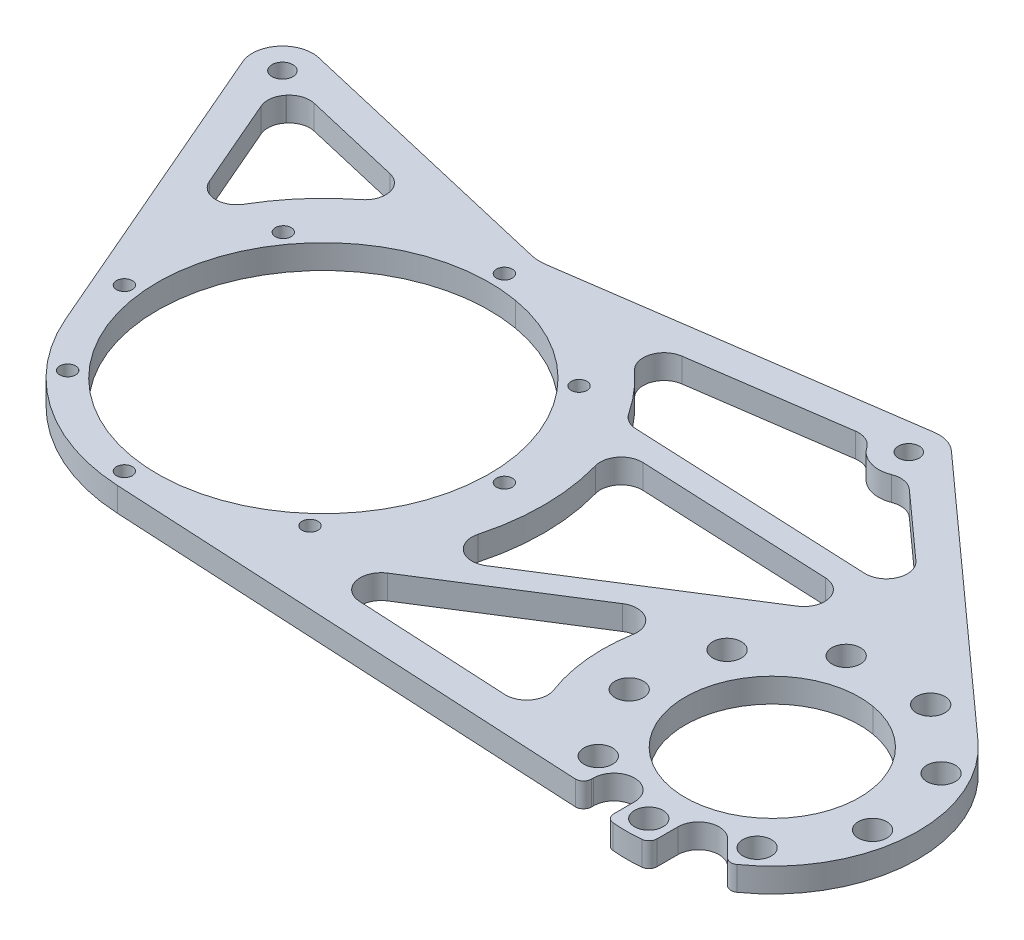
SolidWorks part; units mm, degrees
material "6061-T6 (SS)"
ref_plane "X-Y Datum" through (0, 0, 0) normal (0, 0, 1) x (1, 0, 0)
ref_plane "X-Z Datum" through (0, 0, 0) normal (0, 1, 0) x (1, 0, 0)
ref_plane "Y-Z Datum" through (0, 0, 0) normal (1, 0, 0) x (0, 0, -1)
sketch "Sketch2" plane through (0, 31.3819, 0) normal (0, 1, 0) x (1, 0, 0)
  line L0 (-693.7583, -176.702) -> (-693.7583, -183.2747) construction
  line L1 (-680.0808, -183.2747) -> (-680.0808, -176.702) construction
  line L2 (-668.9846, -172.1058) -> (-663.7197, -177.3707) construction
  line L3 (-693.7583, -176.702) -> (-693.7583, -183.2747)
  line L4 (-680.0808, -183.2747) -> (-680.0808, -176.702)
  line L5 (-668.9846, -172.1058) -> (-663.7197, -177.3707)
  line L6 (-966.641, -0.354) -> (-738.041, -0.354)
  line L7 (-727.7656, -5.5904) -> (-649.7224, -113.0358)
  line L9 (-977.8288, -19.0644) -> (-913.2312, -139.3061)
  line L10 (-706.7583, -177.279) -> (-706.7583, -176.702) construction
  line L11 (-706.7583, -177.279) -> (-706.7583, -176.702)
  line L12 (-861.9259, -171.8334) -> (-709.2983, -179.819)
  line L13 (-858.691, -110.0055) -> (-686.9195, -140.054) construction
  line L14 (-972.26, -24.9963) -> (-955.4664, -39.59) construction
  line L15 (-941.4162, -26.937) -> (-954.1775, -8.712) construction
  line L16 (-751.1929, -14.159) -> (-755.4346, -35.9995) construction
  line L17 (-737.4517, -41.8408) -> (-728.049, -21.6768) construction
  line L18 (-972.26, -24.9963) -> (-955.4664, -39.59)
  line L19 (-941.4162, -26.937) -> (-954.1775, -8.712)
  line L20 (-751.1929, -14.159) -> (-755.4346, -35.9995)
  line L21 (-737.4517, -41.8408) -> (-728.049, -21.6768)
  line L22 (-949.2186, -22.8753) -> (-746.0843, -28.2904)
  line L23 (-739.7146, -30.7335) -> (-656.1751, -105.8723)
  line L24 (-957.9647, -36.1729) -> (-915.5404, -134.527)
  arc A0 (-710.607, -179.4559) -> (-706.7583, -177.279) centre (-709.2983, -177.279) ccw construction
  arc A1 (-693.7583, -176.702) -> (-706.7583, -176.702) centre (-700.2583, -176.702) ccw construction
  arc A2 (-693.7583, -183.2747) -> (-691.4697, -185.8023) centre (-691.2183, -183.2747) ccw construction
  arc A3 (-691.4697, -185.8023) -> (-682.3694, -185.8023) centre (-686.9195, -140.054) ccw construction
  arc A4 (-682.3694, -185.8023) -> (-680.0808, -183.2747) centre (-682.6208, -183.2747) ccw construction
  arc A5 (-668.9846, -172.1058) -> (-680.0808, -176.702) centre (-673.5808, -176.702) ccw construction
  arc A6 (-663.7197, -177.3707) -> (-660.4619, -177.6519) centre (-661.9236, -175.5746) ccw construction
  arc A7 (-660.4619, -177.6519) -> (-710.607, -179.4559) centre (-686.9195, -140.054) ccw construction
  circle A8 centre (-858.691, -110.0055) radius 52.3875 construction
  circle A9 centre (-858.691, -110.0055) radius 61.9125 construction
  circle A10 centre (-738.041, -13.054) radius 12.7 construction
  circle A11 centre (-966.641, -13.054) radius 12.7 construction
  arc A12 (-710.607, -179.4559) -> (-706.7583, -177.279) centre (-709.2983, -177.279) ccw
  arc A13 (-693.7583, -176.702) -> (-706.7583, -176.702) centre (-700.2583, -176.702) ccw
  arc A14 (-693.7583, -183.2747) -> (-691.4697, -185.8023) centre (-691.2183, -183.2747) ccw
  arc A15 (-691.4697, -185.8023) -> (-682.3694, -185.8023) centre (-686.9195, -140.054) ccw
  arc A16 (-682.3694, -185.8023) -> (-680.0808, -183.2747) centre (-682.6208, -183.2747) ccw
  arc A17 (-668.9846, -172.1058) -> (-680.0808, -176.702) centre (-673.5808, -176.702) ccw
  arc A18 (-663.7197, -177.3707) -> (-660.4619, -177.6519) centre (-661.9236, -175.5746) ccw
  arc A19 (-660.4619, -177.6519) -> (-710.607, -179.4559) centre (-686.9195, -140.054) ccw
  circle A20 centre (-858.691, -110.0055) radius 52.3875
  circle A21 centre (-858.691, -110.0055) radius 61.9125
  circle A22 centre (-738.041, -13.054) radius 12.7
  circle A23 centre (-966.641, -13.054) radius 12.7
  circle A24 centre (-901.1618, -148.2463) radius 2.5 construction
  circle A25 centre (-915.528, -115.9793) radius 2.5 construction
  circle A26 centre (-904.9264, -76.4135) radius 2.5 construction
  circle A27 centre (-858.691, -52.8555) radius 2.5 construction
  circle A28 centre (-816.2203, -71.7646) radius 2.5 construction
  circle A29 centre (-801.541, -110.0055) radius 2.5 construction
  circle A30 centre (-820.4502, -152.4762) radius 2.5 construction
  circle A31 centre (-864.6648, -166.8424) radius 2.5 construction
  circle A32 centre (-901.1618, -148.2463) radius 2.5
  circle A33 centre (-915.528, -115.9793) radius 2.5
  circle A34 centre (-904.9264, -76.4135) radius 2.5
  circle A35 centre (-858.691, -52.8555) radius 2.5
  circle A36 centre (-816.2203, -71.7646) radius 2.5
  circle A37 centre (-801.541, -110.0055) radius 2.5
  circle A38 centre (-820.4502, -152.4762) radius 2.5
  circle A39 centre (-864.6648, -166.8424) radius 2.5
  circle A40 centre (-686.9195, -140.054) radius 27.4955 construction
  circle A41 centre (-686.9195, -140.054) radius 27.4955
  circle A42 centre (-711.9883, -169.9297) radius 4.5 construction
  circle A43 centre (-725.3271, -146.8263) radius 4.5 construction
  circle A44 centre (-720.6945, -120.554) radius 4.5 construction
  circle A45 centre (-700.2583, -103.406) radius 4.5 construction
  circle A46 centre (-673.5808, -103.406) radius 4.5 construction
  circle A47 centre (-653.1446, -120.554) radius 4.5 construction
  circle A48 centre (-648.512, -146.8263) radius 4.5 construction
  circle A49 centre (-661.8508, -169.9297) radius 4.5 construction
  circle A50 centre (-686.9195, -179.054) radius 4.5 construction
  circle A51 centre (-711.9883, -169.9297) radius 4.5
  circle A52 centre (-725.3271, -146.8263) radius 4.5
  circle A53 centre (-720.6945, -120.554) radius 4.5
  circle A54 centre (-700.2583, -103.406) radius 4.5
  circle A55 centre (-673.5808, -103.406) radius 4.5
  circle A56 centre (-653.1446, -120.554) radius 4.5
  circle A57 centre (-648.512, -146.8263) radius 4.5
  circle A58 centre (-661.8508, -169.9297) radius 4.5
  circle A59 centre (-686.9195, -179.054) radius 4.5
  circle A60 centre (-966.641, -13.054) radius 3.3
  circle A61 centre (-738.041, -13.054) radius 3.3
  arc A62 (-955.4664, -39.59) -> (-941.4162, -26.937) centre (-949.2186, -32.4003) ccw construction
  arc A63 (-749.3237, -37.1863) -> (-742.8448, -38.4445) centre (-746.0843, -37.8154) ccw construction
  arc A64 (-742.8448, -38.4445) -> (-749.3237, -37.1863) centre (-746.0843, -37.8154) ccw construction
  arc A65 (-755.4346, -35.9995) -> (-737.4517, -41.8408) centre (-746.0843, -37.8154) ccw construction
  arc A66 (-955.4664, -39.59) -> (-941.4162, -26.937) centre (-949.2186, -32.4003) ccw
  arc A67 (-749.3237, -37.1863) -> (-742.8448, -38.4445) centre (-746.0843, -37.8154) ccw
  arc A68 (-742.8448, -38.4445) -> (-749.3237, -37.1863) centre (-746.0843, -37.8154) ccw
  arc A69 (-755.4346, -35.9995) -> (-737.4517, -41.8408) centre (-746.0843, -37.8154) ccw
  circle A70 centre (-949.2186, -32.4003) radius 3.3
  circle A71 centre (-949.2186, -32.4003) radius 9.525
  circle A72 centre (-746.0843, -37.8154) radius 9.525
  point P94 (-949.2186, -32.4003)
  dimension "D1" = 6.6
  dimension "D2" = 6.6
  dimension "D3" = 6.6
extrude "Boss-Extrude1" add sketch "Sketch2" along normal blind 7.62 contours A21 A39 A38 A37 A36 A35 A34 A33 A32 A20 | A18 A19 A12 L11 A13 L3 A14 A15 A16 L4 A17 L5 A59 A58 A57 A56 A55 A54 A53 A52 A51 A41 | L13 A21 L12 A12 A19 | A21 L13 A19 L23 L21 A69 L20 L22 L19 A66 L18 L24 | A69 A72 A68 A67 | A72 L22 L20 | A72 L21 L23 | A71 L24 L18 | A71 L19 L22 | A71 A66 L22 A70 region at (-700.2583, 31.3819, 168.9016) region at (-773.051, 31.3819, 154.3682) region at (-890.9045, 31.3819, 160.8157) region at (-806.8861, 31.3819, 67.2042) region at (-956.9478, 31.3819, 38.0512) region at (-736.2382, 31.3819, 35.8095) region at (-956.6903, 31.3819, 37.8629) region at (-748.9437, 31.3819, 46.6182) region at (-752.4763, 31.3819, 29.8585) region at (-944.5842, 31.3819, 23.8004)
sketch "Sketch3" plane through (0, 31.3819, 0) normal (0, -1, 0) x (1, 0, 0)
  line L1 (-949.2186, 22.8753) -> (-746.0843, 28.2904) construction
  line L5 (-861.9259, 171.8334) -> (-709.2983, 179.819) construction
  line L6 (-977.8288, 19.0644) -> (-913.2312, 139.3061) construction
  line L7 (-727.7656, 5.5904) -> (-649.7224, 113.0358) construction
  line L13 (-751.1929, 14.159) -> (-755.4346, 35.9995) construction
  line L16 (-966.641, 0.354) -> (-738.041, 0.354) construction
  line L19 (-663.7197, 177.3707) -> (-668.9846, 172.1058)
  line L20 (-680.0808, 176.702) -> (-680.0808, 183.2747)
  line L21 (-693.7583, 183.2747) -> (-693.7583, 176.702)
  line L22 (-706.7583, 176.702) -> (-706.7583, 177.279)
  line L23 (-663.7197, 177.3707) -> (-668.9846, 172.1058)
  line L24 (-680.0808, 176.702) -> (-680.0808, 183.2747)
  line L25 (-693.7583, 183.2747) -> (-693.7583, 176.702)
  line L26 (-706.7583, 176.702) -> (-706.7583, 177.279)
  line L28 (-861.9259, 171.8334) -> (-709.2983, 179.819)
  line L29 (-977.8288, 19.0644) -> (-913.2312, 139.3061)
  line L30 (-727.7656, 5.5904) -> (-649.7224, 113.0358)
  line L31 (-966.641, 0.354) -> (-738.041, 0.354)
  line L34 (-737.4517, 41.8408) -> (-728.049, 21.6768) construction
  line L35 (-972.26, 24.9963) -> (-955.4664, 39.59) construction
  line L36 (-947.0539, 23.1246) -> (-856.9722, 44.1471)
  line L37 (-856.9722, 44.1471) -> (-747.4408, 28.3875)
  line L44 (-941.4162, 26.937) -> (-954.1775, 8.712) construction
  line L45 (-957.9647, 36.1729) -> (-915.5404, 134.527) construction
  line L46 (-739.7146, 30.7335) -> (-656.1751, 105.8723) construction
  line L47 (-861.9259, 171.8334) -> (-709.2983, 179.819)
  line L48 (-977.8288, 19.0644) -> (-913.2312, 139.3061)
  line L49 (-727.7656, 5.5904) -> (-649.7224, 113.0358)
  line L50 (-966.641, 0.354) -> (-738.041, 0.354)
  line L51 (-949.2186, 22.8753) -> (-746.0843, 28.2904)
  line L52 (-751.1929, 14.159) -> (-755.4346, 35.9995)
  line L53 (-737.4517, 41.8408) -> (-728.049, 21.6768)
  line L54 (-972.26, 24.9963) -> (-955.4664, 39.59)
  line L55 (-941.4162, 26.937) -> (-954.1775, 8.712)
  line L56 (-957.9647, 36.1729) -> (-915.5404, 134.527)
  line L57 (-739.7146, 30.7335) -> (-656.1751, 105.8723)
  arc A1 (-737.4517, 41.8408) -> (-755.4346, 35.9995) centre (-746.0843, 37.8154) ccw construction
  circle A3 centre (-966.641, 13.054) radius 12.7
  circle A5 centre (-966.641, 13.054) radius 12.7
  circle A7 centre (-738.041, 13.054) radius 12.7
  circle A9 centre (-738.041, 13.054) radius 12.7
  circle A11 centre (-858.691, 110.0055) radius 61.9125
  circle A13 centre (-858.691, 110.0055) radius 61.9125
  circle A15 centre (-858.691, 110.0055) radius 52.3875
  circle A17 centre (-858.691, 110.0055) radius 52.3875
  circle A19 centre (-686.9195, 140.054) radius 27.4955
  circle A21 centre (-686.9195, 140.054) radius 27.4955
  circle A23 centre (-864.6648, 166.8424) radius 2.5
  circle A25 centre (-864.6648, 166.8424) radius 2.5
  circle A27 centre (-820.4502, 152.4762) radius 2.5
  circle A29 centre (-820.4502, 152.4762) radius 2.5
  circle A31 centre (-801.541, 110.0055) radius 2.5
  circle A33 centre (-801.541, 110.0055) radius 2.5
  circle A35 centre (-816.2203, 71.7646) radius 2.5
  circle A37 centre (-816.2203, 71.7646) radius 2.5
  circle A39 centre (-858.691, 52.8555) radius 2.5
  circle A41 centre (-858.691, 52.8555) radius 2.5
  circle A43 centre (-904.9264, 76.4135) radius 2.5
  circle A46 centre (-904.9264, 76.4135) radius 2.5
  circle A47 centre (-915.528, 115.9793) radius 2.5
  circle A48 centre (-915.528, 115.9793) radius 2.5
  circle A49 centre (-901.1618, 148.2463) radius 2.5
  circle A50 centre (-901.1618, 148.2463) radius 2.5
  circle A51 centre (-720.6945, 120.554) radius 4.5
  circle A52 centre (-720.6945, 120.554) radius 4.5
  circle A68 centre (-725.3271, 146.8263) radius 4.5
  circle A69 centre (-725.3271, 146.8263) radius 4.5
  circle A70 centre (-711.9883, 169.9297) radius 4.5
  circle A71 centre (-711.9883, 169.9297) radius 4.5
  circle A72 centre (-738.041, 13.054) radius 3.3
  circle A73 centre (-738.041, 13.054) radius 3.3
  circle A74 centre (-966.641, 13.054) radius 3.3
  circle A75 centre (-966.641, 13.054) radius 3.3
  circle A76 centre (-686.9195, 179.054) radius 4.5
  circle A77 centre (-686.9195, 179.054) radius 4.5
  circle A78 centre (-661.8508, 169.9297) radius 4.5
  circle A79 centre (-661.8508, 169.9297) radius 4.5
  circle A80 centre (-648.512, 146.8263) radius 4.5
  circle A81 centre (-648.512, 146.8263) radius 4.5
  circle A82 centre (-653.1446, 120.554) radius 4.5
  circle A83 centre (-653.1446, 120.554) radius 4.5
  circle A84 centre (-673.5808, 103.406) radius 4.5
  circle A85 centre (-673.5808, 103.406) radius 4.5
  circle A86 centre (-700.2583, 103.406) radius 4.5
  circle A87 centre (-700.2583, 103.406) radius 4.5
  arc A95 (-710.607, 179.4559) -> (-660.4619, 177.6519) centre (-686.9195, 140.054) ccw
  arc A96 (-660.4619, 177.6519) -> (-663.7197, 177.3707) centre (-661.9236, 175.5746) ccw
  arc A97 (-680.0808, 176.702) -> (-668.9846, 172.1058) centre (-673.5808, 176.702) ccw
  arc A98 (-680.0808, 183.2747) -> (-682.3694, 185.8023) centre (-682.6208, 183.2747) ccw
  arc A99 (-682.3694, 185.8023) -> (-691.4697, 185.8023) centre (-686.9195, 140.054) ccw
  arc A100 (-691.4697, 185.8023) -> (-693.7583, 183.2747) centre (-691.2183, 183.2747) ccw
  arc A101 (-706.7583, 176.702) -> (-693.7583, 176.702) centre (-700.2583, 176.702) ccw
  arc A102 (-706.7583, 177.279) -> (-710.607, 179.4559) centre (-709.2983, 177.279) ccw
  arc A103 (-710.607, 179.4559) -> (-660.4619, 177.6519) centre (-686.9195, 140.054) ccw
  arc A104 (-660.4619, 177.6519) -> (-663.7197, 177.3707) centre (-661.9236, 175.5746) ccw
  arc A105 (-680.0808, 176.702) -> (-668.9846, 172.1058) centre (-673.5808, 176.702) ccw
  arc A106 (-680.0808, 183.2747) -> (-682.3694, 185.8023) centre (-682.6208, 183.2747) ccw
  arc A107 (-682.3694, 185.8023) -> (-691.4697, 185.8023) centre (-686.9195, 140.054) ccw
  arc A108 (-691.4697, 185.8023) -> (-693.7583, 183.2747) centre (-691.2183, 183.2747) ccw
  arc A109 (-706.7583, 176.702) -> (-693.7583, 176.702) centre (-700.2583, 176.702) ccw
  arc A110 (-706.7583, 177.279) -> (-710.607, 179.4559) centre (-709.2983, 177.279) ccw
  circle A152 centre (-746.0843, 37.8154) radius 9.525
  circle A153 centre (-746.0843, 37.8154) radius 9.525
  circle A154 centre (-949.2186, 32.4003) radius 9.525
  circle A155 centre (-949.2186, 32.4003) radius 9.525
  circle A156 centre (-949.2186, 32.4003) radius 3.3
  circle A157 centre (-949.2186, 32.4003) radius 3.3
  arc A158 (-941.4162, 26.937) -> (-955.4664, 39.59) centre (-949.2186, 32.4003) ccw construction
  arc A159 (-742.8448, 38.4445) -> (-749.3237, 37.1863) centre (-746.0843, 37.8154) ccw
  arc A160 (-749.3237, 37.1863) -> (-742.8448, 38.4445) centre (-746.0843, 37.8154) ccw
  arc A161 (-742.8448, 38.4445) -> (-749.3237, 37.1863) centre (-746.0843, 37.8154) ccw
  arc A162 (-749.3237, 37.1863) -> (-742.8448, 38.4445) centre (-746.0843, 37.8154) ccw
  arc A163 (-737.4517, 41.8408) -> (-755.4346, 35.9995) centre (-746.0843, 37.8154) ccw
  arc A164 (-941.4162, 26.937) -> (-955.4664, 39.59) centre (-949.2186, 32.4003) ccw
  dimension "D24" = 0
  dimension "D25" = 0
  dimension "D26" = 90.0818
  dimension "D27" = 21.0225
  dimension "D1" = 0
  dimension "D2" = 0
  dimension "D3" = 0
  dimension "D4" = 0
  dimension "D5" = 0
  dimension "D6" = 0
  dimension "D7" = 0
  dimension "D8" = 0
  dimension "D9" = 0
  dimension "D10" = 0
  dimension "D11" = 0
  dimension "D12" = 0
  dimension "D13" = 0
  dimension "D14" = 0
  dimension "D15" = 0
  dimension "D16" = 0
  dimension "D17" = 0
  dimension "D18" = 0
  dimension "D19" = 0
  dimension "D20" = 0
  dimension "D21" = 0
  dimension "D22" = 0
  dimension "D23" = 0
  dimension "D52" = 0
  dimension "D53" = 0
  dimension "D54" = 0
  dimension "D55" = 0
ref_point "Point1"
ref_point "Point2"
ref_plane "Plane1" through (-858.691, 31.3819, 110.0055) normal (0.985, 0, 0.1723) x (0.1723, 0, -0.985)
ref_plane "Plane2" through (-686.9195, 31.3819, 140.054) normal (-0.985, 0, -0.1723) x (-0.1723, 0, 0.985)
split line "Split Line1"
split line "Split Line2"
ref_axis "Axis1" through (-858.691, 39.0019, 110.0055) along (0, -1, 0)
ref_axis "Axis2" through (-686.9195, 39.0019, 140.054) along (0, -1, 0)
extrude "Cut-Extrude1" cut sketch "Sketch3" against normal through all contours L36 L55 L51 L52 L37 | A155 L51 L55 L36 | A153 L37 L52 L51 region at (-751.5495, 31.3819, 28.5688) region at (-850.6911, 31.3819, 31.7926) region at (-945.2616, 31.3819, 23.2848)
fillet "Fillet2" radius 12.7 1 edges at (-856.9722, 35.1919, 44.1471)
sketch "Sketch4" plane through (0, 31.3819, 0) normal (0, -1, 0) x (1, 0, 0)
  line L0 (-861.9259, 171.8334) -> (-709.2983, 179.819) construction
  line L1 (-727.7656, 5.5904) -> (-649.7224, 113.0358) construction
  line L2 (-977.8288, 19.0644) -> (-913.2312, 139.3061) construction
  line L4 (-706.7583, 176.702) -> (-706.7583, 177.279)
  line L5 (-663.7197, 177.3707) -> (-668.9846, 172.1058)
  line L6 (-680.0808, 176.702) -> (-680.0808, 183.2747)
  line L7 (-693.7583, 183.2747) -> (-693.7583, 176.702)
  line L8 (-706.7583, 176.702) -> (-706.7583, 177.279)
  line L9 (-663.7197, 177.3707) -> (-668.9846, 172.1058)
  line L10 (-680.0808, 176.702) -> (-680.0808, 183.2747)
  line L11 (-693.7583, 183.2747) -> (-693.7583, 176.702)
  line L13 (-966.641, 0.354) -> (-738.041, 0.354) construction
  line L14 (-861.9259, 171.8334) -> (-709.2983, 179.819)
  line L15 (-727.7656, 5.5904) -> (-649.7224, 113.0358)
  line L16 (-977.8288, 19.0644) -> (-913.2312, 139.3061)
  line L17 (-861.9259, 171.8334) -> (-709.2983, 179.819) construction
  line L19 (-966.641, 0.354) -> (-738.041, 0.354)
  line L20 (-924.6037, 87.863) -> (-948.1369, 33.3048)
  line L21 (-948.1369, 33.3048) -> (-888.5504, 47.2106)
  line L22 (-732.3805, 168.4374) -> (-812.7818, 164.2308)
  line L23 (-812.7818, 164.2308) -> (-733.9678, 114.3873)
  line L24 (-799.833, 147.0258) -> (-703.8013, 86.2934)
  line L25 (-703.8013, 86.2934) -> (-794.9695, 82.1785)
  line L26 (-824.108, 49.6832) -> (-755.4008, 39.7974)
  line L27 (-798.9847, 74.3695) -> (-701.5009, 78.7695)
  line L28 (-701.5009, 78.7695) -> (-739.4428, 44.643)
  line L29 (-977.8288, 19.0644) -> (-913.2312, 139.3061) construction
  line L30 (-727.7656, 5.5904) -> (-649.7224, 113.0358) construction
  line L31 (-966.641, 0.354) -> (-738.041, 0.354) construction
  line L32 (-663.7197, 177.3707) -> (-668.9846, 172.1058)
  line L33 (-680.0808, 176.702) -> (-680.0808, 183.2747)
  line L34 (-693.7583, 183.2747) -> (-693.7583, 176.702)
  line L35 (-706.7583, 176.702) -> (-706.7583, 177.279)
  line L36 (-663.7197, 177.3707) -> (-668.9846, 172.1058)
  line L37 (-680.0808, 176.702) -> (-680.0808, 183.2747)
  line L38 (-693.7583, 183.2747) -> (-693.7583, 176.702)
  line L39 (-706.7583, 176.702) -> (-706.7583, 177.279)
  line L40 (-949.2186, 22.8753) -> (-746.0843, 28.2904) construction
  line L41 (-751.1929, 14.159) -> (-755.4346, 35.9995) construction
  line L42 (-737.4517, 41.8408) -> (-728.049, 21.6768) construction
  line L43 (-972.26, 24.9963) -> (-955.4664, 39.59) construction
  line L44 (-941.4162, 26.937) -> (-954.1775, 8.712) construction
  line L45 (-957.9647, 36.1729) -> (-915.5404, 134.527) construction
  line L46 (-739.7146, 30.7335) -> (-656.1751, 105.8723) construction
  line L47 (-861.9259, 171.8334) -> (-709.2983, 179.819)
  line L48 (-977.8288, 19.0644) -> (-913.2312, 139.3061)
  line L49 (-727.7656, 5.5904) -> (-649.7224, 113.0358)
  line L50 (-966.641, 0.354) -> (-738.041, 0.354)
  line L51 (-949.2186, 22.8753) -> (-746.0843, 28.2904)
  line L52 (-751.1929, 14.159) -> (-755.4346, 35.9995)
  line L53 (-737.4517, 41.8408) -> (-728.049, 21.6768)
  line L54 (-972.26, 24.9963) -> (-955.4664, 39.59)
  line L55 (-941.4162, 26.937) -> (-954.1775, 8.712)
  line L56 (-957.9647, 36.1729) -> (-915.5404, 134.527)
  line L57 (-739.7146, 30.7335) -> (-656.1751, 105.8723)
  line L58 (-947.0539, 23.1246) -> (-859.3005, 43.6037) construction
  line L60 (-854.6056, 43.8066) -> (-747.4408, 28.3875) construction
  circle A1 centre (-858.691, 110.0055) radius 52.3875
  circle A2 centre (-858.691, 110.0055) radius 52.3875
  circle A3 centre (-858.691, 110.0055) radius 61.9125
  circle A4 centre (-858.691, 110.0055) radius 61.9125
  circle A5 centre (-738.041, 13.054) radius 12.7
  circle A6 centre (-738.041, 13.054) radius 12.7
  circle A7 centre (-966.641, 13.054) radius 12.7
  circle A8 centre (-966.641, 13.054) radius 12.7
  circle A9 centre (-858.691, 52.8555) radius 2.5
  circle A10 centre (-858.691, 52.8555) radius 2.5
  circle A11 centre (-816.2203, 71.7646) radius 2.5
  circle A12 centre (-816.2203, 71.7646) radius 2.5
  circle A13 centre (-801.541, 110.0055) radius 2.5
  circle A14 centre (-801.541, 110.0055) radius 2.5
  circle A15 centre (-820.4502, 152.4762) radius 2.5
  circle A16 centre (-820.4502, 152.4762) radius 2.5
  circle A17 centre (-864.6648, 166.8424) radius 2.5
  circle A18 centre (-864.6648, 166.8424) radius 2.5
  circle A19 centre (-686.9195, 140.054) radius 27.4955
  circle A20 centre (-686.9195, 140.054) radius 27.4955
  circle A21 centre (-725.3271, 146.8263) radius 4.5
  circle A22 centre (-725.3271, 146.8263) radius 4.5
  circle A23 centre (-720.6945, 120.554) radius 4.5
  circle A24 centre (-720.6945, 120.554) radius 4.5
  circle A25 centre (-901.1618, 148.2463) radius 2.5
  circle A26 centre (-901.1618, 148.2463) radius 2.5
  circle A27 centre (-915.528, 115.9793) radius 2.5
  circle A28 centre (-915.528, 115.9793) radius 2.5
  circle A29 centre (-904.9264, 76.4135) radius 2.5
  circle A30 centre (-904.9264, 76.4135) radius 2.5
  circle A31 centre (-661.8508, 169.9297) radius 4.5
  circle A32 centre (-661.8508, 169.9297) radius 4.5
  circle A33 centre (-686.9195, 179.054) radius 4.5
  circle A34 centre (-686.9195, 179.054) radius 4.5
  circle A35 centre (-966.641, 13.054) radius 3.3
  circle A36 centre (-966.641, 13.054) radius 3.3
  circle A37 centre (-738.041, 13.054) radius 3.3
  circle A38 centre (-738.041, 13.054) radius 3.3
  circle A39 centre (-711.9883, 169.9297) radius 4.5
  circle A40 centre (-711.9883, 169.9297) radius 4.5
  circle A41 centre (-700.2583, 103.406) radius 4.5
  circle A42 centre (-700.2583, 103.406) radius 4.5
  circle A43 centre (-673.5808, 103.406) radius 4.5
  circle A44 centre (-673.5808, 103.406) radius 4.5
  circle A45 centre (-653.1446, 120.554) radius 4.5
  circle A46 centre (-653.1446, 120.554) radius 4.5
  circle A47 centre (-648.512, 146.8263) radius 4.5
  circle A48 centre (-648.512, 146.8263) radius 4.5
  arc A49 (-888.5504, 47.2106) -> (-924.6037, 87.863) centre (-858.691, 110.0055) cw
  arc A50 (-732.3805, 168.4374) -> (-733.9678, 114.3873) centre (-686.9195, 140.054) ccw
  arc A51 (-799.833, 147.0258) -> (-794.9695, 82.1785) centre (-858.691, 110.0055) cw
  arc A52 (-824.108, 49.6832) -> (-798.9847, 74.3695) centre (-858.691, 110.0055) ccw
  arc A53 (-737.4517, 41.8408) -> (-755.4346, 35.9995) centre (-746.0843, 37.8154) ccw construction
  circle A54 centre (-966.641, 13.054) radius 12.7
  circle A55 centre (-966.641, 13.054) radius 12.7
  arc A56 (-706.7583, 177.279) -> (-710.607, 179.4559) centre (-709.2983, 177.279) ccw
  arc A57 (-710.607, 179.4559) -> (-660.4619, 177.6519) centre (-686.9195, 140.054) ccw
  arc A58 (-660.4619, 177.6519) -> (-663.7197, 177.3707) centre (-661.9236, 175.5746) ccw
  arc A59 (-680.0808, 176.702) -> (-668.9846, 172.1058) centre (-673.5808, 176.702) ccw
  arc A60 (-680.0808, 183.2747) -> (-682.3694, 185.8023) centre (-682.6208, 183.2747) ccw
  arc A61 (-682.3694, 185.8023) -> (-691.4697, 185.8023) centre (-686.9195, 140.054) ccw
  arc A62 (-691.4697, 185.8023) -> (-693.7583, 183.2747) centre (-691.2183, 183.2747) ccw
  arc A63 (-706.7583, 176.702) -> (-693.7583, 176.702) centre (-700.2583, 176.702) ccw
  arc A64 (-706.7583, 177.279) -> (-710.607, 179.4559) centre (-709.2983, 177.279) ccw
  arc A65 (-710.607, 179.4559) -> (-660.4619, 177.6519) centre (-686.9195, 140.054) ccw
  arc A66 (-660.4619, 177.6519) -> (-663.7197, 177.3707) centre (-661.9236, 175.5746) ccw
  arc A67 (-680.0808, 176.702) -> (-668.9846, 172.1058) centre (-673.5808, 176.702) ccw
  arc A68 (-680.0808, 183.2747) -> (-682.3694, 185.8023) centre (-682.6208, 183.2747) ccw
  arc A69 (-682.3694, 185.8023) -> (-691.4697, 185.8023) centre (-686.9195, 140.054) ccw
  arc A70 (-691.4697, 185.8023) -> (-693.7583, 183.2747) centre (-691.2183, 183.2747) ccw
  arc A71 (-706.7583, 176.702) -> (-693.7583, 176.702) centre (-700.2583, 176.702) ccw
  circle A72 centre (-738.041, 13.054) radius 12.7
  circle A73 centre (-738.041, 13.054) radius 12.7
  circle A74 centre (-858.691, 110.0055) radius 61.9125
  circle A75 centre (-858.691, 110.0055) radius 61.9125
  circle A76 centre (-858.691, 110.0055) radius 52.3875
  circle A77 centre (-858.691, 110.0055) radius 52.3875
  circle A78 centre (-686.9195, 140.054) radius 27.4955
  circle A79 centre (-686.9195, 140.054) radius 27.4955
  circle A80 centre (-864.6648, 166.8424) radius 2.5
  circle A81 centre (-864.6648, 166.8424) radius 2.5
  circle A82 centre (-820.4502, 152.4762) radius 2.5
  circle A83 centre (-820.4502, 152.4762) radius 2.5
  circle A84 centre (-801.541, 110.0055) radius 2.5
  circle A85 centre (-801.541, 110.0055) radius 2.5
  circle A86 centre (-816.2203, 71.7646) radius 2.5
  circle A87 centre (-816.2203, 71.7646) radius 2.5
  circle A88 centre (-858.691, 52.8555) radius 2.5
  circle A89 centre (-858.691, 52.8555) radius 2.5
  circle A90 centre (-904.9264, 76.4135) radius 2.5
  circle A91 centre (-904.9264, 76.4135) radius 2.5
  circle A92 centre (-915.528, 115.9793) radius 2.5
  circle A93 centre (-915.528, 115.9793) radius 2.5
  circle A94 centre (-901.1618, 148.2463) radius 2.5
  circle A95 centre (-901.1618, 148.2463) radius 2.5
  circle A96 centre (-720.6945, 120.554) radius 4.5
  circle A97 centre (-720.6945, 120.554) radius 4.5
  circle A98 centre (-725.3271, 146.8263) radius 4.5
  circle A99 centre (-725.3271, 146.8263) radius 4.5
  circle A100 centre (-711.9883, 169.9297) radius 4.5
  circle A101 centre (-711.9883, 169.9297) radius 4.5
  circle A102 centre (-738.041, 13.054) radius 3.3
  circle A103 centre (-738.041, 13.054) radius 3.3
  circle A104 centre (-966.641, 13.054) radius 3.3
  circle A105 centre (-966.641, 13.054) radius 3.3
  circle A106 centre (-686.9195, 179.054) radius 4.5
  circle A107 centre (-686.9195, 179.054) radius 4.5
  circle A108 centre (-661.8508, 169.9297) radius 4.5
  circle A109 centre (-661.8508, 169.9297) radius 4.5
  circle A110 centre (-648.512, 146.8263) radius 4.5
  circle A111 centre (-648.512, 146.8263) radius 4.5
  circle A112 centre (-653.1446, 120.554) radius 4.5
  circle A113 centre (-653.1446, 120.554) radius 4.5
  circle A114 centre (-673.5808, 103.406) radius 4.5
  circle A115 centre (-673.5808, 103.406) radius 4.5
  circle A116 centre (-700.2583, 103.406) radius 4.5
  circle A117 centre (-700.2583, 103.406) radius 4.5
  circle A118 centre (-746.0843, 37.8154) radius 9.525
  circle A119 centre (-746.0843, 37.8154) radius 9.525
  circle A120 centre (-949.2186, 32.4003) radius 9.525
  circle A121 centre (-949.2186, 32.4003) radius 9.525
  circle A122 centre (-949.2186, 32.4003) radius 3.3
  circle A123 centre (-949.2186, 32.4003) radius 3.3
  arc A124 (-941.4162, 26.937) -> (-955.4664, 39.59) centre (-949.2186, 32.4003) ccw construction
  arc A125 (-742.8448, 38.4445) -> (-749.3237, 37.1863) centre (-746.0843, 37.8154) ccw
  arc A126 (-749.3237, 37.1863) -> (-742.8448, 38.4445) centre (-746.0843, 37.8154) ccw
  arc A127 (-742.8448, 38.4445) -> (-749.3237, 37.1863) centre (-746.0843, 37.8154) ccw
  arc A128 (-749.3237, 37.1863) -> (-742.8448, 38.4445) centre (-746.0843, 37.8154) ccw
  arc A129 (-737.4517, 41.8408) -> (-755.4346, 35.9995) centre (-746.0843, 37.8154) ccw
  arc A130 (-941.4162, 26.937) -> (-955.4664, 39.59) centre (-949.2186, 32.4003) ccw
  arc A135 (-710.607, 179.4559) -> (-660.4619, 177.6519) centre (-686.9195, 140.054) ccw
  arc A136 (-660.4619, 177.6519) -> (-663.7197, 177.3707) centre (-661.9236, 175.5746) ccw
  arc A137 (-680.0808, 176.702) -> (-668.9846, 172.1058) centre (-673.5808, 176.702) ccw
  arc A138 (-680.0808, 183.2747) -> (-682.3694, 185.8023) centre (-682.6208, 183.2747) ccw
  arc A139 (-682.3694, 185.8023) -> (-691.4697, 185.8023) centre (-686.9195, 140.054) ccw
  arc A140 (-691.4697, 185.8023) -> (-693.7583, 183.2747) centre (-691.2183, 183.2747) ccw
  arc A141 (-706.7583, 176.702) -> (-693.7583, 176.702) centre (-700.2583, 176.702) ccw
  arc A142 (-706.7583, 177.279) -> (-710.607, 179.4559) centre (-709.2983, 177.279) ccw
  arc A143 (-710.607, 179.4559) -> (-660.4619, 177.6519) centre (-686.9195, 140.054) ccw
  arc A144 (-660.4619, 177.6519) -> (-663.7197, 177.3707) centre (-661.9236, 175.5746) ccw
  arc A145 (-680.0808, 176.702) -> (-668.9846, 172.1058) centre (-673.5808, 176.702) ccw
  arc A146 (-680.0808, 183.2747) -> (-682.3694, 185.8023) centre (-682.6208, 183.2747) ccw
  arc A147 (-682.3694, 185.8023) -> (-691.4697, 185.8023) centre (-686.9195, 140.054) ccw
  arc A148 (-691.4697, 185.8023) -> (-693.7583, 183.2747) centre (-691.2183, 183.2747) ccw
  arc A149 (-706.7583, 176.702) -> (-693.7583, 176.702) centre (-700.2583, 176.702) ccw
  arc A150 (-706.7583, 177.279) -> (-710.607, 179.4559) centre (-709.2983, 177.279) ccw
  dimension "D26" = 7.62
  dimension "D29" = 7.62
  dimension "D30" = 7.62
  dimension "D35" = 0
  dimension "D39" = 7.62
  dimension "D27" = 0
  dimension "D28" = 0
  dimension "D31" = 10.16
  dimension "D32" = 7.62
  dimension "D33" = 93.2524
  dimension "D34" = 49.8435
  dimension "D36" = 91.1683
  dimension "D37" = 4.1149
  dimension "D38" = 10.16
  dimension "D40" = 7.62
  dimension "D67" = 10.16
  dimension "D68" = 10.16
  dimension "D69" = 10.16
  dimension "D1" = 0
  dimension "D2" = 0
  dimension "D3" = 0
  dimension "D4" = 0
  dimension "D5" = 0
  dimension "D6" = 0
  dimension "D7" = 0
  dimension "D8" = 0
  dimension "D9" = 0
  dimension "D10" = 0
  dimension "D11" = 0
  dimension "D12" = 0
  dimension "D13" = 0
  dimension "D14" = 0
  dimension "D15" = 0
  dimension "D16" = 0
  dimension "D17" = 0
  dimension "D18" = 0
  dimension "D19" = 0
  dimension "D20" = 0
  dimension "D21" = 0
  dimension "D22" = 0
  dimension "D23" = 0
  dimension "D24" = 0
  dimension "D25" = 0
  dimension "D41" = 0
  dimension "D42" = 0
  dimension "D43" = 0
  dimension "D44" = 0
  dimension "D45" = 0
  dimension "D46" = 0
  dimension "D47" = 0
  dimension "D48" = 0
  dimension "D49" = 0
  dimension "D50" = 0
  dimension "D51" = 0
  dimension "D52" = 0
  dimension "D53" = 0
  dimension "D54" = 0
  dimension "D55" = 0
  dimension "D56" = 0
  dimension "D57" = 0
  dimension "D58" = 0
  dimension "D59" = 0
  dimension "D60" = 0
  dimension "D61" = 0
  dimension "D62" = 0
  dimension "D63" = 0
  dimension "D64" = 0
  dimension "D65" = 0
  dimension "D66" = 0
extrude "Cut-Extrude2" cut sketch "Sketch4" against normal through all contours L21 A49 L20 A8 | A52 L26 A6 L28 L27 | L24 A51 L25 | A50 L22 L23 region at (-763.7407, 31.3819, 60.8107) region at (-921.8341, 31.3819, 54.9859) region at (-763.0306, 31.3819, 150.0769) region at (-762.4094, 31.3819, 103.8535)
fillet "Fillet3" radius 6.604 15 edges at (-733.9678, 35.1919, 114.3873) (-732.3805, 35.1919, 168.4374) (-812.7818, 35.1919, 164.2308) (-703.8013, 35.1919, 86.2934) (-794.9695, 35.1919, 82.1785) (-799.833, 35.1919, 147.0258) (-701.5009, 35.1919, 78.7695) (-798.9847, 35.1919, 74.3695) (-824.108, 35.1919, 49.6832) (-888.5504, 35.1919, 47.2106) (-924.6037, 35.1919, 87.863) (-739.4428, 35.1919, 44.643) (-755.4008, 35.1919, 39.7974) (-940.1078, 35.1919, 35.1786) (-944.8714, 35.1919, 40.8754)
split line "Split Line3"
sketch "Sketch2<4>" plane through (0, 31.3819, 0) normal (0, 1, 0) x (1, 0, 0) same geometry as "Sketch2"
